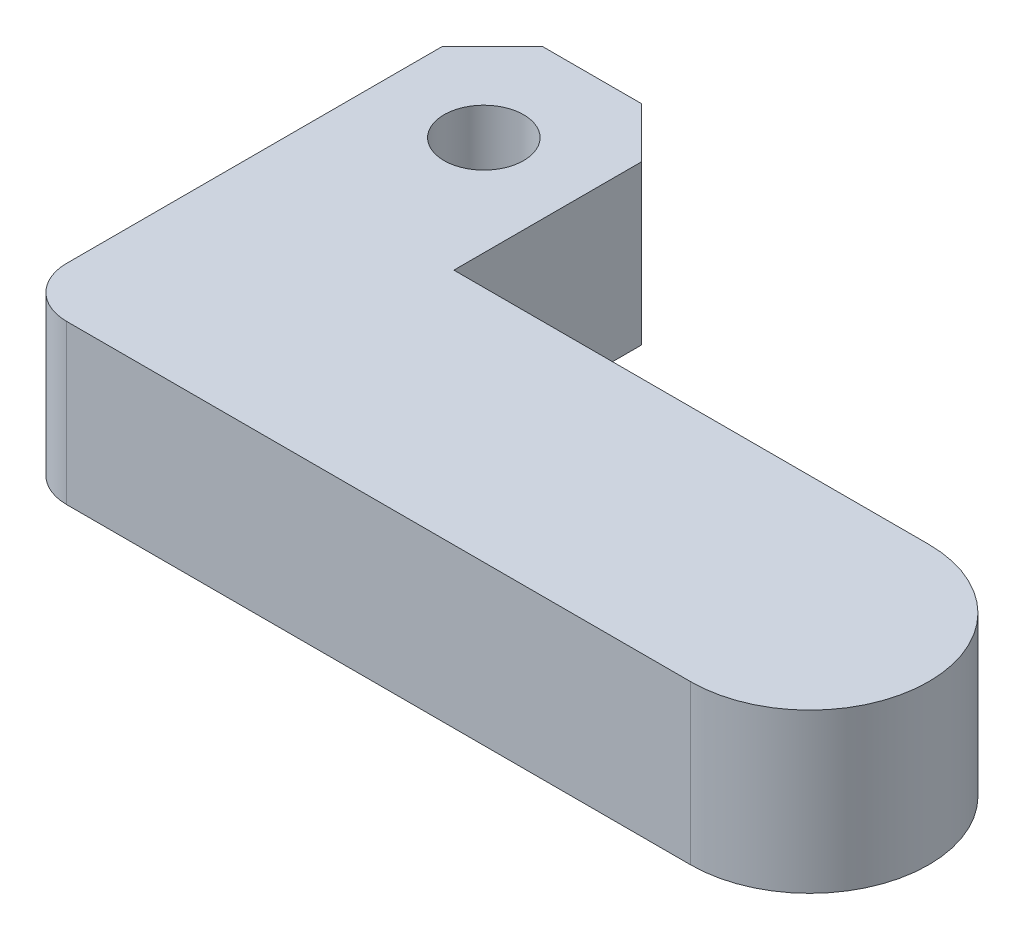
SolidWorks part; units mm, degrees
ref_plane "Front" through (0, 0, 0) normal (0, 0, 1) x (1, 0, 0)
ref_plane "Top" through (0, 0, 0) normal (0, 1, 0) x (1, 0, 0)
ref_plane "Right" through (0, 0, 0) normal (1, 0, 0) x (0, 0, -1)
sketch "Sketch1" plane through (0, 0, 0) normal (0, 1, 0) x (1, 0, 0)
  line L0 (0, 30) -> (0, 0)
  line L1 (0, 0) -> (42.5, 0)
  line L3 (42.5, 15) -> (12.573, 15)
  line L4 (12.573, 15) -> (12.573, 30)
  line L5 (12.573, 30) -> (0, 30)
  circle A0 centre (6.2865, 23.175) radius 2.5082
  arc A1 (42.5, 0) -> (42.5, 15) centre (42.5, 7.5) ccw
  point P2 (0, 0)
  point P6 (0, 0)
  point P10 (6.2865, 30)
  point P11 (50.466, 6.2824)
  point P14 (50, 0)
  point P15 (0, 0)
  point P16 (45.4363, 15)
  dimension "D4" = 5.0165
  dimension "D6" = 7.5
  dimension "D5" = 8.175
  dimension "D3" = 50
  dimension "D1" = 12.573
  dimension "D2" = 30
  dimension "D7" = 15
extrude "Boss-Extrude1" add sketch "Sketch1" along normal blind 10
fillet "Fillet1" radius 3.175 1 edges at (0, 5, 0)
chamfer "Chamfer1" distance 3.175 angle 45 2 edges at (0, 5, -30) (12.573, 5, -30)
